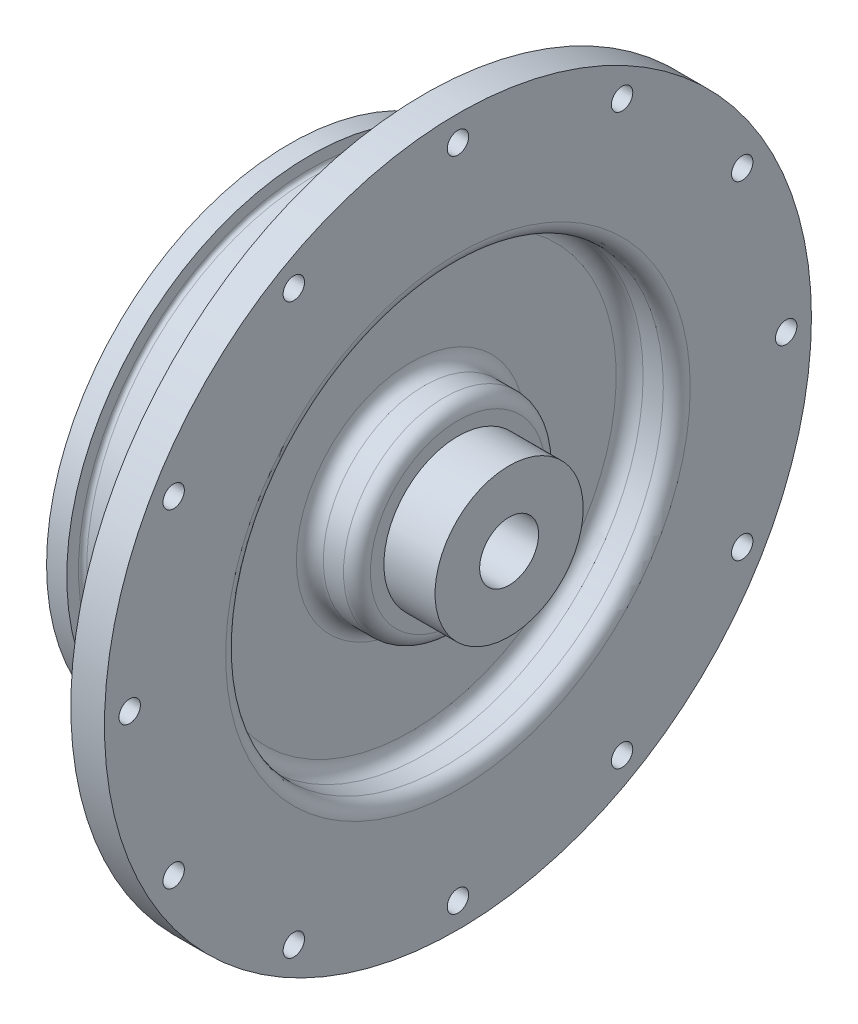
SolidWorks part; units mm, degrees
material "7075-T6 (SN)"
ref_plane "Front Plane" through (0, 0, 0) normal (0, 0, 1) x (1, 0, 0)
ref_plane "Top Plane" through (0, 0, 0) normal (0, 1, 0) x (1, 0, 0)
ref_plane "Right Plane" through (0, 0, 0) normal (1, 0, 0) x (0, 0, -1)
sketch "Sketch1" plane through (0, 0, 0) normal (1, 0, 0) x (0, 0, -1)
  circle A0 centre (0, 0) radius 66.675
  dimension "D1" = 133.35
extrude "Boss-Extrude1" add sketch "Sketch1" along normal blind 6.35
sketch "Sketch2" plane through (0, 0, 0) normal (-1, 0, 0) x (0, 0, 1)
  circle A0 centre (0, 0) radius 45.847
  dimension "D1" = 91.694
extrude "Boss-Extrude2" add sketch "Sketch2" along normal blind 25.4
sketch "Sketch10" plane through (0, 0, 0) normal (0, 1, 0) x (1, 0, 0)
  line L0 (0, 0) -> (-53.2238, 0) construction
  line L1 (-26.2636, 0) -> (26.2636, 0) construction
  line L2 (0, 0) -> (0, 64.5447) construction
  line L3 (0, -62.865) -> (0, 62.865) construction
ref_plane "Plane1" through (0, 0, -45.847) normal (0, 0, -1) x (-1, 0, 0)
sketch "Sketch11" plane through (0, 0, -45.847) normal (0, 0, -1) x (-1, 0, 0)
  line L0 (0, 0) -> (53.2238, 0) construction
  line L1 (0, -45.847) -> (0, 45.847) construction
  circle A0 centre (7.62, 0) radius 1.8986
  dimension "D2" = 3.7973
  dimension "D1" = 7.62
extrude "Cut-Extrude3" cut sketch "Sketch11" against normal blind 10.16
pattern_circular "CirPattern1" count 10 every 36 about axis through (0, 0, 0) along (-1, 0, 0) of "Cut-Extrude3" reverse direction yes
sketch "Sketch15" plane through (6.35, 0, 0) normal (1, 0, 0) x (0, 0, -1)
  circle A0 centre (0, 0) radius 5.5562
  dimension "D1" = 11.1125
extrude "Cut-Extrude4" cut sketch "Sketch15" against normal through all both and the other way through all
sketch "Sketch16" plane through (0, 0, 0) normal (0, 0, 1) x (1, 0, 0)
  line L0 (0, 45.847) -> (-25.4, 45.847) construction
  line L1 (-21.59, 45.847) -> (-14.4018, 45.847)
  line L2 (-21.59, 45.847) -> (-21.59, 43.6245)
  line L3 (-20.828, 42.8625) -> (-15.1638, 42.8625)
  line L4 (-14.4018, 45.847) -> (-14.4018, 43.6245)
  line L5 (0, 0) -> (-53.2238, 0) construction
  line L6 (-25.4, 45.847) -> (-25.4, -45.847) construction
  arc A0 (-14.4018, 43.6245) -> (-15.1638, 42.8625) centre (-15.1638, 43.6245) cw
  arc A1 (-20.828, 42.8625) -> (-21.59, 43.6245) centre (-20.828, 43.6245) cw
  point P8 (-26.6119, 0)
  point P13 (-14.4018, 42.8625)
  point P16 (-21.59, 42.8625)
  dimension "D4" = 0.762
  dimension "D1" = 42.8625
  dimension "D2" = 3.81
  dimension "D3" = 7.1882
revolve "Cut-Revolve1" cut sketch "Sketch16" angle 360 about L0
sketch "Sketch17" plane through (6.35, 0, 0) normal (1, 0, 0) x (0, 0, -1)
  circle A0 centre (0, 0) radius 13.97
  circle A1 centre (0, 0) radius 5.5562
  dimension "D1" = 27.94
  dimension "D2" = 11.1125
extrude "Boss-Extrude3" add sketch "Sketch17" along normal blind 9.652
cosmetic thread "Cosmetic Thread1" parameters "D2"=23.1953
sketch "Sketch18" plane through (0, 0, 0) normal (0, 0, 1) x (1, 0, 0)
  line L0 (6.35, -66.675) -> (6.35, 66.675) construction
  line L1 (6.35, 41.275) -> (-2.54, 41.275)
  line L2 (6.35, 41.275) -> (6.35, 19.05)
  line L3 (6.35, 19.05) -> (-2.54, 19.05)
  line L4 (-2.54, 41.275) -> (-2.54, 19.05)
  line L5 (0, 0) -> (-53.2238, 0) construction
  dimension "D1" = 8.89
  dimension "D2" = 19.05
  dimension "D3" = 41.275
revolve "Cut-Revolve2" cut sketch "Sketch18" angle 360 about L0
fillet "Fillet1" radius 2.54 4 edges at (6.35, 0, -41.275) (-2.54, 0, -41.275) (-2.54, 0, -19.05) (6.35, 0, -19.05)
sketch "Sketch19" plane through (6.35, 0, 0) normal (1, 0, 0) x (0, 0, -1)
  line L0 (0, 0) -> (0, 61.9125) construction
  circle A0 centre (0, 0) radius 57.15 construction
  circle A1 centre (0, 0) radius 61.9125 construction
  circle A2 centre (0, 61.9125) radius 2.0193
  circle A3 centre (30.9563, 53.6178) radius 2.0193
  circle A4 centre (53.6178, 30.9563) radius 2.0193
  circle A5 centre (61.9125, 0) radius 2.0193
  circle A6 centre (53.6178, -30.9562) radius 2.0193
  circle A7 centre (30.9563, -53.6178) radius 2.0193
  circle A8 centre (0, -61.9125) radius 2.0193
  circle A9 centre (-30.9562, -53.6178) radius 2.0193
  circle A10 centre (-53.6178, -30.9563) radius 2.0193
  circle A11 centre (-61.9125, 0) radius 2.0193
  circle A12 centre (-53.6178, 30.9562) radius 2.0193
  circle A13 centre (-30.9562, 53.6178) radius 2.0193
  point P30 (0, 0)
  dimension "D1" = 114.3
  dimension "D2" = 123.825
  dimension "D3" = 4.0386
  dimension "D4" = 12
extrude "Cut-Extrude5" cut sketch "Sketch19" against normal through all
